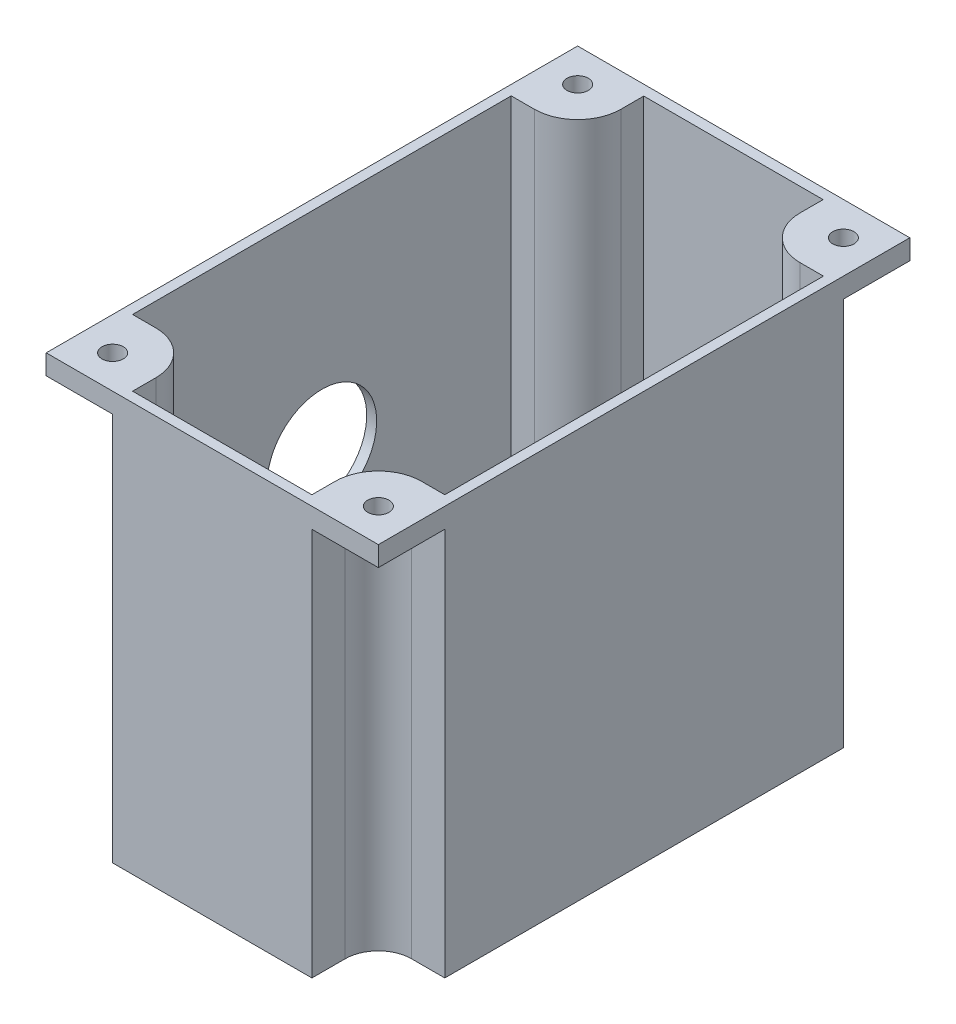
SolidWorks part; units mm, degrees
ref_plane "Płaszczyzna przednia" through (0, 0, 0) normal (0, 0, 1) x (1, 0, 0)
ref_plane "Płaszczyzna górna" through (0, 0, 0) normal (0, 1, 0) x (1, 0, 0)
ref_plane "Płaszczyzna prawa" through (0, 0, 0) normal (1, 0, 0) x (0, 0, -1)
sketch "Sketch1" plane through (0, 0, 0) normal (0, 1, 0) x (1, 0, 0)
  line L4 (23.5, 28.5) -> (23.5, -28.5)
  line L9 (-25, -40) -> (25, -40)
  line L16 (-25, -40) -> (-25, 40)
  line L21 (-25, 40) -> (25, 40)
  line L23 (25, -40) -> (25, 40)
  line L27 (-25, -30) -> (-25, 30)
  line L29 (25, -30) -> (25, 30)
  line L30 (25, 40) -> (15, 40)
  line L31 (25, 40) -> (25, 30)
  line L32 (25, 30) -> (20, 30)
  line L33 (15, 40) -> (15, 35)
  line L34 (25, -40) -> (15, -40)
  line L35 (25, -40) -> (25, -30)
  line L36 (25, -30) -> (20, -30)
  line L37 (15, -40) -> (15, -35)
  line L38 (-25, -40) -> (-15, -40)
  line L39 (-25, -40) -> (-25, -30)
  line L40 (-25, -30) -> (-20, -30)
  line L41 (-15, -40) -> (-15, -35)
  line L42 (-25, 40) -> (-15, 40)
  line L43 (-25, 40) -> (-25, 30)
  line L44 (-25, 30) -> (-20, 30)
  line L45 (-15, 40) -> (-15, 35)
  line L46 (25, 40) -> (13.5, 40)
  line L47 (25, 40) -> (25, 28.5)
  line L48 (23.5, 28.5) -> (20, 28.5)
  line L49 (13.5, 38.45) -> (13.5, 35)
  line L50 (25, -40) -> (13.5, -40)
  line L51 (25, -40) -> (25, -28.5)
  line L52 (23.5, -28.5) -> (20, -28.5)
  line L53 (13.5, -38.5) -> (13.5, -35)
  line L54 (-25, 40) -> (-13.5, 40)
  line L55 (-25, 40) -> (-25, 28.5)
  line L56 (-23.5, 28.5) -> (-20, 28.5)
  line L57 (-13.5, 38.45) -> (-13.5, 35)
  line L58 (-25, -40) -> (-13.5, -40)
  line L59 (-25, -40) -> (-25, -28.5)
  line L60 (-23.5, -28.5) -> (-20, -28.5)
  line L61 (-13.5, -38.5) -> (-13.5, -35)
  line L62 (13.5, -38.5) -> (-13.5, -38.5)
  line L63 (-23.5, -28.5) -> (-23.5, 28.5)
  line L64 (-13.5, 38.45) -> (13.5, 38.45)
  arc A0 (-20, 30) -> (-15, 35) centre (-20, 35) ccw
  arc A1 (-20, -30) -> (-15, -35) centre (-20, -35) cw
  arc A2 (20, -30) -> (15, -35) centre (20, -35) ccw
  arc A3 (20, 30) -> (15, 35) centre (20, 35) cw
  arc A4 (20, 28.5) -> (13.5, 35) centre (20, 35) cw
  arc A5 (20, -28.5) -> (13.5, -35) centre (20, -35) ccw
  arc A6 (-20, -28.5) -> (-13.5, -35) centre (-20, -35) cw
  arc A7 (-20, 28.5) -> (-13.5, 35) centre (-20, 35) ccw
  point P0 (0, 0)
  point P1 (0, 0)
  point P5 (0, 0)
  point P8 (0, 0)
  point P11 (0, 0)
  point P14 (0, 0)
  point P27 (-15, -30)
  point P32 (15, 30)
  point P47 (13.5, 28.5)
  point P50 (13.5, -28.5)
  point P55 (-13.5, 28.5)
  point P56 (23.5, 28.5)
  point P59 (13.5, -38.5)
  point P62 (-23.5, -28.5)
  point P65 (-13.5, 38.45)
  dimension "D6" = 5
  dimension "D11" = 6.5
  dimension "D1" = 50
  dimension "D2" = 80
  dimension "D3" = 50
  dimension "D4" = 10
  dimension "D5" = 10
  dimension "D7" = 11.5
  dimension "D8" = 11.5
  dimension "D9" = 11.5
  dimension "D10" = 11.5
  dimension "D12" = 1.5
  dimension "D13" = 1.5
  dimension "D14" = 1.5
  dimension "D15" = 1.55
extrude "Boss-Extrude6" add sketch "Sketch1" along normal blind 60 contours L16 L23 region at (-14.0566, 0, 37.5)
sketch "Sketch7" plane through (0, 0, 0) normal (0, -1, 0) x (1, 0, 0)
  line L0 (-15, 40) -> (15, 40)
  line L5 (15, 40) -> (15, 35)
  line L6 (20, 30) -> (25, 30)
  line L7 (25, 30) -> (25, -30)
  line L8 (25, -30) -> (20, -30)
  line L9 (15, -35) -> (15, -40)
  line L10 (15, -40) -> (-15, -40)
  line L11 (-15, -40) -> (-15, -35)
  line L12 (-20, -30) -> (-25, -30)
  line L13 (-25, -30) -> (-25, 30)
  line L14 (-25, 30) -> (-20, 30)
  line L15 (-15, 35) -> (-15, 40)
  arc A0 (-20, 30) -> (-15, 35) centre (-20, 35) ccw
  arc A1 (-15, -35) -> (-20, -30) centre (-20, -35) ccw
  arc A2 (20, -30) -> (15, -35) centre (20, -35) ccw
  arc A3 (15, 35) -> (20, 30) centre (20, 35) ccw
  dimension "D1" = 5
extrude "Boss-Extrude8" add sketch "Sketch7" along normal blind 1.5
sketch "Sketch12" plane through (0, 60, 0) normal (0, 1, 0) x (1, 0, 0)
  line L0 (-25, 40) -> (-15, 40)
  line L1 (-25, 30) -> (-15, 30) construction
  line L2 (-25, 30) -> (-25, 40) construction
  line L3 (-25, 40) -> (-15, 40) construction
  line L4 (-15, 30) -> (-15, 40) construction
  line L5 (15, 40) -> (25, 40) construction
  line L6 (15, 40) -> (15, 30) construction
  line L7 (15, 30) -> (25, 30) construction
  line L8 (25, 40) -> (25, 30) construction
  line L9 (-25, -30) -> (-15, -30) construction
  line L10 (-25, -30) -> (-25, -40) construction
  line L11 (-25, -40) -> (-15, -40) construction
  line L12 (-15, -30) -> (-15, -40) construction
  line L13 (15, -40) -> (25, -40) construction
  line L14 (15, -40) -> (15, -30) construction
  line L15 (15, -30) -> (25, -30) construction
  line L16 (25, -40) -> (25, -30) construction
  line L17 (-15, 40) -> (-15, 35)
  line L18 (-20, 30) -> (-25, 30)
  line L19 (-25, 30) -> (-25, 40)
  line L20 (15, 40) -> (25, 40)
  line L21 (25, 40) -> (25, 30)
  line L22 (25, 30) -> (20, 30)
  line L23 (15, 35) -> (15, 40)
  line L24 (20, -30) -> (25, -30)
  line L25 (25, -30) -> (25, -40)
  line L26 (25, -40) -> (15, -40)
  line L27 (15, -40) -> (15, -35)
  line L28 (-15, -40) -> (-25, -40)
  line L29 (-25, -40) -> (-25, -30)
  line L30 (-25, -30) -> (-20, -30)
  line L31 (-15, -35) -> (-15, -40)
  arc A0 (-15, 35) -> (-20, 30) centre (-20, 35) cw
  arc A1 (20, 30) -> (15, 35) centre (20, 35) cw
  arc A2 (20, -30) -> (15, -35) centre (20, -35) ccw
  arc A3 (-20, -30) -> (-15, -35) centre (-20, -35) cw
  dimension "D1" = 5
extrude "Boss-Extrude9" add sketch "Sketch12" against normal blind 3
sketch "Sketch15" plane through (0, 60, 0) normal (0, 1, 0) x (1, 0, 0)
  circle A0 centre (-20, -35) radius 1.6
  circle A1 centre (20, -35) radius 1.6
  circle A2 centre (20, 35) radius 1.6
  circle A3 centre (-20, 35) radius 1.6
extrude "Cut-Extrude4" cut sketch "Sketch15" against normal through all
sketch "Sketch11" plane through (-25, 0, 0) normal (-1, 0, 0) x (0, 0, 1)
  line L0 (-30, 27.75) -> (30, 27.75) construction
  line L3 (-30, 57) -> (-30, -1.5) construction
  line L5 (30, 57) -> (30, -1.5) construction
  line L7 (30, 27.75) -> (0, 60) construction
  line L8 (40, 60) -> (-40, 60) construction
  line L9 (0, 60) -> (0, -1.5) construction
  line L10 (30, -1.5) -> (-30, -1.5) construction
  circle A1 centre (0, 27.75) radius 8.25
extrude "Cut-Extrude3" cut sketch "Sketch11" against normal blind 1.5
